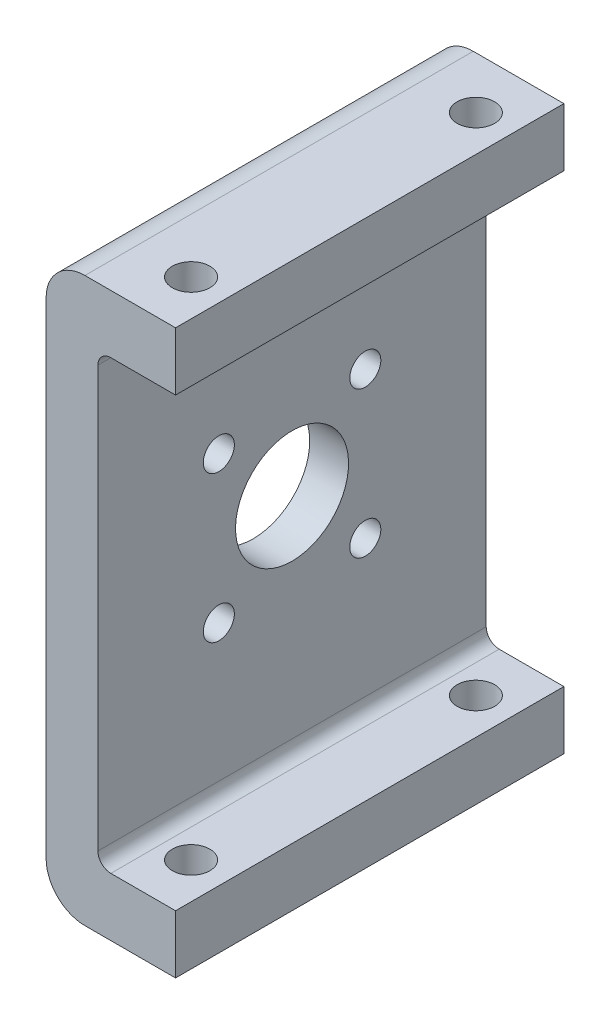
SolidWorks part; units mm, degrees
material "Onyx w/ CF"
ref_plane "Front Plane" through (0, 0, 0) normal (0, 0, 1) x (1, 0, 0)
ref_plane "Top Plane" through (0, 0, 0) normal (0, 1, 0) x (1, 0, 0)
ref_plane "Right Plane" through (0, 0, 0) normal (1, 0, 0) x (0, 0, -1)
other "Center of Mass"
sketch "Sketch2" plane through (0, 0, 0) normal (0, 0, 1) x (1, 0, 0)
  line L0 (0, 21.75) -> (0, -21.75)
  line L1 (0, -21.75) -> (10, -21.75)
  line L2 (10, -21.75) -> (10, -17.25)
  line L3 (10, -17.25) -> (4, -17.25)
  line L4 (4, -17.25) -> (4, 17.25)
  line L5 (4, 17.25) -> (10, 17.25)
  line L6 (10, 17.25) -> (10, 21.75)
  line L7 (10, 21.75) -> (0, 21.75)
  point P4 (0, 0)
  dimension "D1" = 4.5
  dimension "D2" = 4
  dimension "D3" = 6
  dimension "D4" = 34.5
extrude "Boss-Extrude1" add sketch "Sketch2" along normal mid plane 30
hole_wizard "M2.5 Clearance Hole1" positions "Sketch6" profile "Sketch7" hole size "M2.5" standard "ANSI Metric" end condition through all
sketch "Sketch6" plane through (0, -21.75, 0) normal (0, -1, 0) x (-1, 0, 0)
  line L0 (-7.2, 11) -> (-7.2, -11)
  line L2 (-10, -15) -> (-10, 15) construction
  point P0 (-7.2, -11)
  point P2 (-7.2, 11)
  point P15 (-7.2, 0)
  dimension "D1" = 2.8
  dimension "D2" = 22
sketch "Sketch7" plane through (7.2, -21.75, 11) normal (1, 0, 0) x (0, 0, -1)
  line L0 (0, 0) -> (0, 43.5)
  line L1 (0, 43.5) -> (1.45, 43.5)
  line L2 (1.45, 43.5) -> (1.45, 0)
  line L5 (1.45, 0) -> (0, 0)
  line L11 (0, -6.35) -> (0, 107.95) construction
  dimension "Thru Hole Dia." = 2.9
  dimension "Thru Hole Depth" = 43.5
sketch "Sketch3" plane through (4, 0, 0) normal (1, 0, 0) x (0, 0, -1)
  circle A0 centre (0, 0) radius 4.3656
  dimension "D1" = 8.7312
extrude "Cut-Extrude1" cut sketch "Sketch3" against normal through all both and the other way through all
hole_wizard "M2 Clearance Hole1" positions "Sketch4" profile "Sketch5" hole size "M2" standard "ANSI Metric" end condition through all
sketch "Sketch4" plane through (0, 0, 0) normal (-1, 0, 0) x (0, 0, 1)
  line L1 (5.6569, 5.6569) -> (-5.6569, 5.6569)
  line L2 (5.6569, 5.6569) -> (5.6569, -5.6569)
  line L3 (5.6569, -5.6569) -> (-5.6569, -5.6569)
  line L4 (-5.6569, 5.6569) -> (-5.6569, -5.6569)
  line L5 (5.6569, 5.6569) -> (-5.6569, -5.6569) construction
  line L6 (5.6569, -5.6569) -> (-5.6569, 5.6569) construction
  point P0 (5.6569, 5.6569)
  point P2 (5.6569, -5.6569)
  point P4 (-5.6569, -5.6569)
  point P6 (-5.6569, 5.6569)
  point P9 (0, 0)
  dimension "D1" = 11.3137
sketch "Sketch5" plane through (0, 5.6569, 5.6569) normal (0, 1, 0) x (0, 0, 1)
  line L0 (0, 0) -> (0, 10)
  line L1 (0, 10) -> (1.2, 10)
  line L2 (1.2, 10) -> (1.2, 0)
  line L5 (1.2, 0) -> (0, 0)
  line L11 (0, -6.35) -> (0, 107.95) construction
  dimension "Thru Hole Dia." = 2.4
  dimension "Thru Hole Depth" = 10
sketch "Sketch10" plane through (0, 0, 0) normal (-1, 0, 0) x (0, 0, 1)
  circle A0 centre (0, 0) radius 11.5
  dimension "D1" = 23
extrude "Cut-Extrude3" cut sketch "Sketch10" against normal blind 1
fillet "Fillet1" radius 1 2 edges at (4, -17.25, 0) (4, 17.25, 0)
fillet "Fillet2" radius 3 2 edges at (0, -21.75, 0) (0, 21.75, 0)
